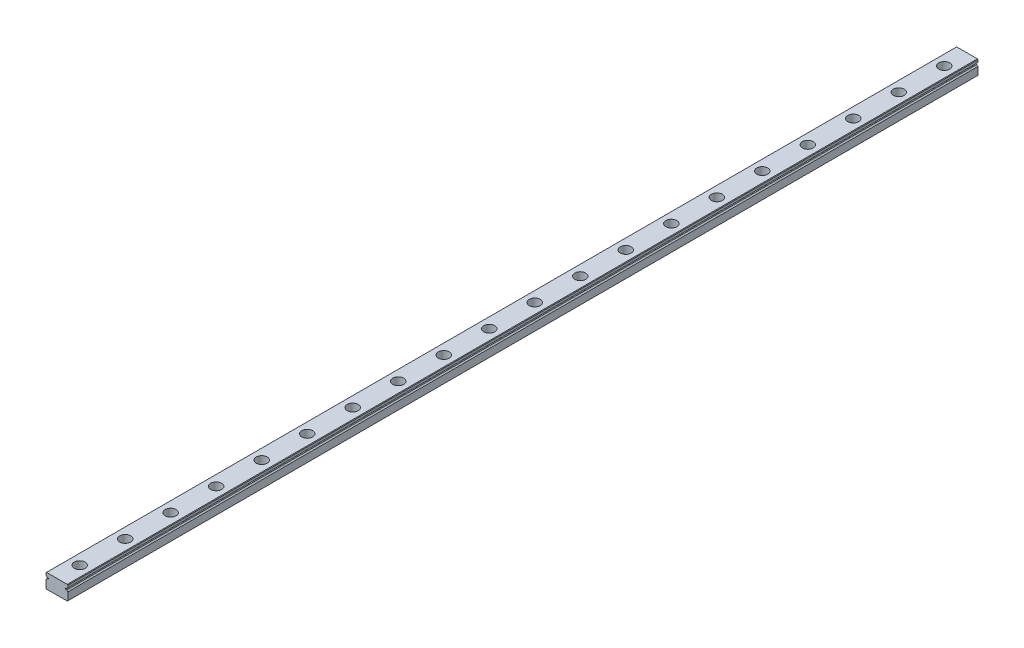
SolidWorks part; units mm, degrees
ref_plane "Спереди" through (0, 0, 0) normal (0, 0, 1) x (1, 0, 0)
ref_plane "Сверху" through (0, 0, 0) normal (0, 1, 0) x (1, 0, 0)
ref_plane "Справа" through (0, 0, 0) normal (1, 0, 0) x (0, 0, -1)
sketch "Эскиз1" plane through (0, 0, 0) normal (0, 0, 1) x (1, 0, 0)
  line L0 (-6, 3.7) -> (-5.7, 4)
  line L1 (-5.7, -4) -> (5.7, -4)
  line L2 (-6, -3.7) -> (-6, 0.549)
  line L3 (-5.7, 4) -> (5.7, 4)
  line L4 (6, -3.7) -> (6, 0.549)
  line L5 (-6, -4) -> (6, 4) construction
  line L6 (-6, 4) -> (6, -4) construction
  line L7 (-6, -3.7) -> (-5.7, -4)
  line L8 (5.7, -4) -> (6, -3.7)
  line L9 (5.7, 4) -> (6, 3.7)
  line L10 (-6, 2.451) -> (-6, 3.7)
  line L11 (-5.3546, 1.7981) -> (-4.6435, 1.7981)
  line L12 (0, 5.4188) -> (0, -5.747) construction
  line L13 (-5.3546, 1.2019) -> (-4.6435, 1.2019)
  line L14 (-4.6435, 1.7981) -> (-4.6435, 1.2019)
  line L15 (4.6435, 1.7981) -> (4.6435, 1.2019)
  line L16 (5.3546, 1.2019) -> (4.6435, 1.2019)
  line L17 (5.3546, 1.7981) -> (4.6435, 1.7981)
  line L18 (6, 2.451) -> (6, 3.7)
  line L19 (4.6435, 1.7981) -> (5.3546, 1.7981) construction
  arc A0 (-6, 0.549) -> (-5.3546, 1.2019) centre (-6.3091, 1.5) ccw
  arc A1 (-5.3546, 1.7981) -> (-6, 2.451) centre (-6.3091, 1.5) ccw
  arc A2 (5.3546, 1.7981) -> (6, 2.451) centre (6.3091, 1.5) cw
  arc A3 (6, 0.549) -> (5.3546, 1.2019) centre (6.3091, 1.5) cw
  point P0 (0, 0)
extrude "Бобышка-Вытянуть1" add sketch "Эскиз1" along normal blind 500
sketch "Эскиз2" plane through (0, 4, 0) normal (0, 1, 0) x (1, 0, 0)
  line L0 (0, 0) -> (0, -26.2396) construction
  line L1 (5.7, 0) -> (-5.7, 0) construction
  line L2 (-3.8306, -12.5) -> (3.8306, -12.5) construction
  circle A0 centre (0, -12.5) radius 3
  circle A1 centre (0, -12.5) radius 1.75
  dimension "D2" = 3.5
  dimension "D3" = 6
  dimension "D1" = 12.5
extrude "Вырез-Вытянуть1" cut sketch "Эскиз2" against normal blind 4.5
extrude "Вырез-Вытянуть2" cut sketch "Эскиз2<2>" against normal through all contours A1 region at (0, 4, 12.5)
sketch "Эскиз2<2>" plane through (0, 4, 0) normal (0, 1, 0) x (1, 0, 0) same geometry as "Эскиз2"
pattern_linear "Линейный массив1" count 20 spacing 25 along (0, 0, 1) of "Вырез-Вытянуть1", "Вырез-Вытянуть2"
